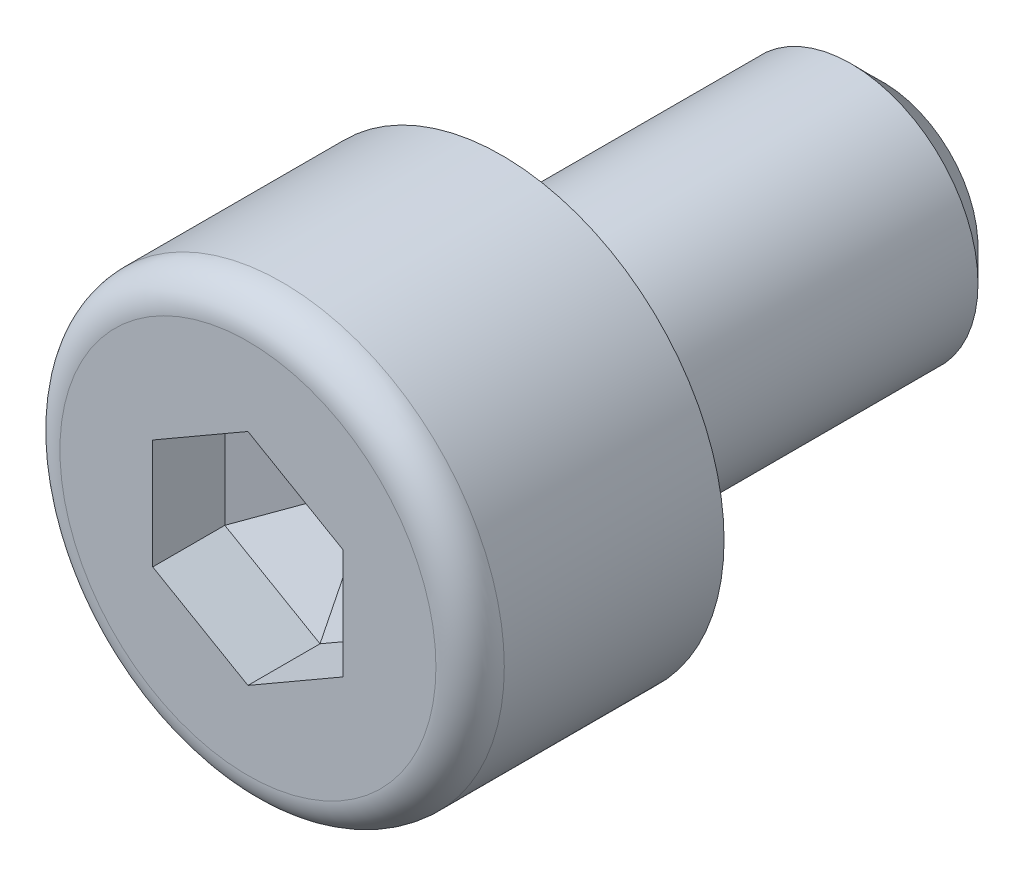
SolidWorks part; units mm, degrees
ref_plane "前视基准面" through (0, 0, 0) normal (0, 0, 1) x (1, 0, 0)
ref_plane "上视基准面" through (0, 0, 0) normal (0, 1, 0) x (1, 0, 0)
ref_plane "右视基准面" through (0, 0, 0) normal (1, 0, 0) x (0, 0, -1)
sketch "草图1" plane through (0, 0, 0) normal (0, 0, 1) x (1, 0, 0)
  circle A0 centre (0, 0) radius 3.5
  dimension "dk" = 7
extrude "凸台-拉伸1" add sketch "草图1" along normal blind 4
ref_axis "基准轴1" through (0, 0, 4) along (0, 0, -1)
sketch "草图2" plane through (0, 0, 4) normal (0, 0, 1) x (1, 0, 0)
  line L1 (1.5, 0.866) -> (0, 1.7321)
  line L2 (0, 1.7321) -> (-1.5, 0.866)
  line L3 (-1.5, 0.866) -> (-1.5, -0.866)
  line L4 (-1.5, -0.866) -> (0, -1.7321)
  line L5 (0, -1.7321) -> (1.5, -0.866)
  line L6 (1.5, -0.866) -> (1.5, 0.866)
  circle A0 centre (0, 0) radius 1.5 construction
  dimension "s" = 3
extrude "切除-拉伸1" cut sketch "草图2" against normal blind 2
sketch "草图3" plane through (0, 0, 0) normal (0, 0, -1) x (-1, 0, 0)
  circle A0 centre (0, 0) radius 2
  dimension "d" = 4
extrude "凸台-拉伸2" add sketch "草图3" along normal blind 6
cosmetic thread "装饰螺纹线1" parameters "b"=4.9, "D2"=1.221
chamfer "倒角1" distance 0.5 angle 45 1 edges at (-2, 0, -6)
fillet "圆角1" radius 0.5385 1 edges at (3.5, 0, 4)
chamfer "倒角2" distance 0.8646 angle 60 6 edges at (-1.5, 0, 2) (-0.75, 1.299, 2) (0.75, 1.299, 2) (1.5, 0, 2) (-0.75, -1.299, 2) (0.75, -1.299, 2) first distance on face at (-1.5, 0, 3) first distance on face at (-0.75, 1.299, 3) first distance on face at (0.75, 1.299, 3) first distance on face at (1.5, 0, 3) first distance on face at (-0.75, -1.299, 3) first distance on face at (0.75, -1.299, 3)
fillet "圆角2" radius 0.1 1 edges at (2, 0, 0)
ref_plane "基准面1" through (0, 0, 0) normal (0, 0, -1) x (-1, 0, 0)
equation "\"D1@倒角2\" = \"s@草图2\" / 3.47"
equation "\"D1@圆角1\"= \"dk@草图1\" / 13"
equation "\"D1@倒角1\"= \"d@草图3\" / 8"
equation "\"D1@圆角2\"= \"d@草图3\" / \"d@草图3\" * 0.1"
